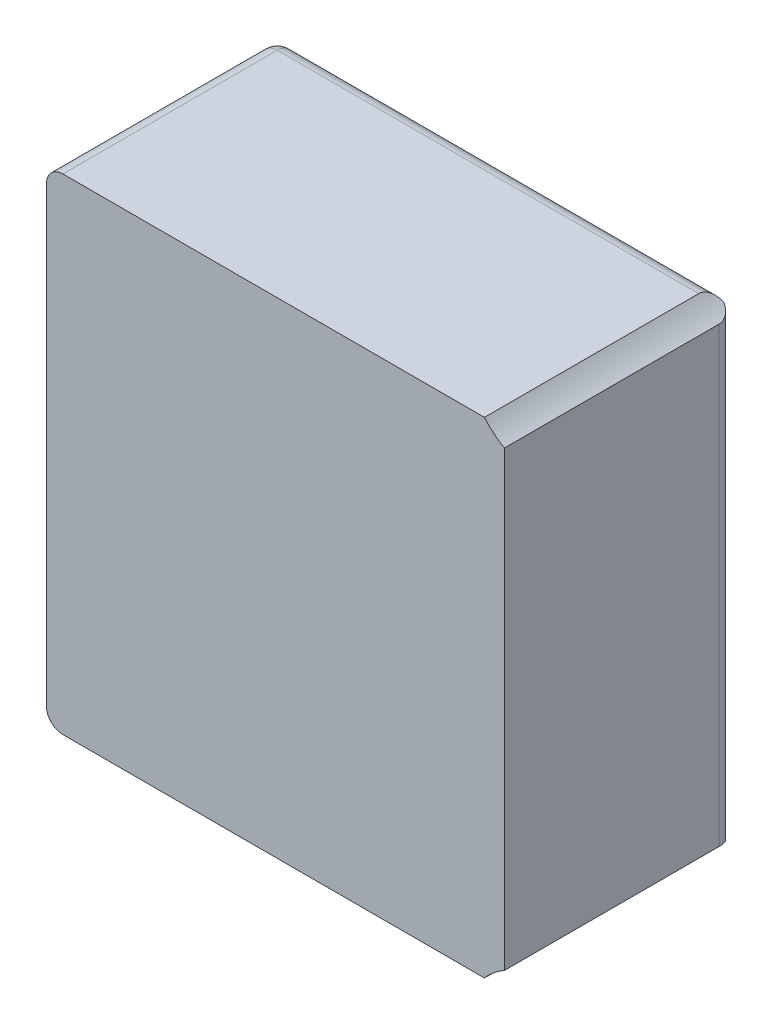
SolidWorks part; units mm, degrees
ref_plane "Front Plane" through (0, 0, 0) normal (0, 0, 1) x (1, 0, 0)
ref_plane "Top Plane" through (0, 0, 0) normal (0, 1, 0) x (1, 0, 0)
ref_plane "Right Plane" through (0, 0, 0) normal (1, 0, 0) x (0, 0, -1)
sketch "Sketch1" plane through (0, 0, 0) normal (0, 0, 1) x (1, 0, 0)
  line L30 (71.0405, 34.9049) -> (71.0405, 5.4536)
  line L31 (98.8249, 33.901) -> (98.8249, 6.4576)
  line L58 (97.6105, 5.4536) -> (71.0405, 5.4536)
  line L59 (71.0405, 34.9049) -> (97.6105, 34.9049)
  spline S2 degree 3 poles (98.8249, 33.901) (98.3549, 34.1567) (97.9574, 34.5001) (97.6105, 34.9049) knots 0 0 0 0 1 1 1 1
  spline S3 degree 3 poles (97.6105, 5.4536) (97.9574, 5.8584) (98.3549, 6.2018) (98.8249, 6.4576) knots 0 0 0 0 1 1 1 1
extrude "Boss-Extrude1" add sketch "Sketch1" along normal blind 14
fillet "Fillet1" radius 1 4 edges at (71.0405, 20.1793, 0)
fillet "Fillet2" radius 1 4 edges at (71.3334, 34.612, 0.2929) (71.3334, 5.7465, 0.2929) (71.0405, 34.9049, 7.5) (71.0405, 5.4536, 7.5)
